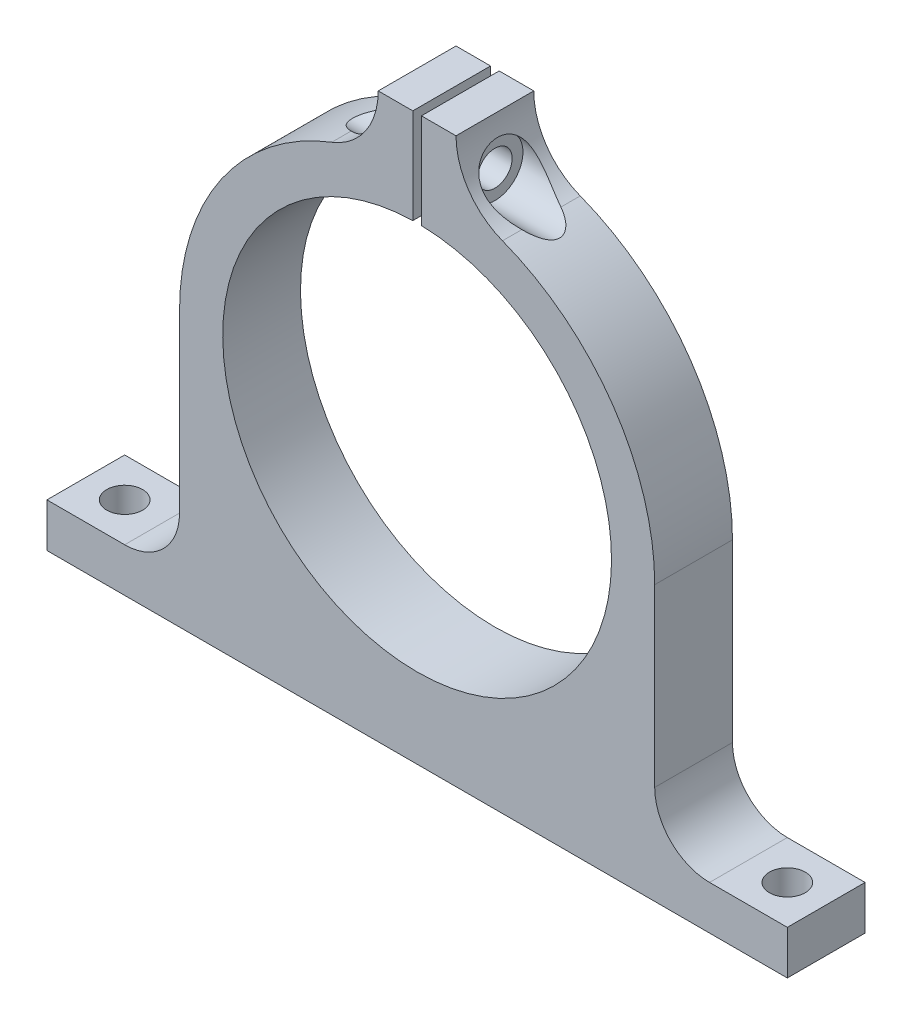
SolidWorks part; units mm, degrees
ref_plane "Front Plane" through (0, 0, 0) normal (0, 0, 1) x (1, 0, 0)
ref_plane "Top Plane" through (0, 0, 0) normal (0, 1, 0) x (1, 0, 0)
ref_plane "Right Plane" through (0, 0, 0) normal (1, 0, 0) x (0, 0, -1)
sketch "Sketch1" plane through (0, 0, 0) normal (0, 0, 1) x (1, 0, 0)
  line L0 (0, 0) -> (0, 55) construction
  line L1 (0, 0) -> (85.7, 0) construction
  line L2 (0, 0) -> (-85.7, 0) construction
  line L3 (85.7, -53.34) -> (85.7, -63.5)
  line L4 (85.7, -63.5) -> (-85.7, -63.5)
  line L5 (-85.7, -63.5) -> (-85.7, -53.34)
  line L6 (0, 55) -> (0, 67) construction
  line L7 (0, 67) -> (1, 67) construction
  line L8 (1, 67) -> (1, 44.9889)
  line L9 (1, 67) -> (9, 67)
  line L10 (-45, 0) -> (-55, 0) construction
  line L11 (0, 67) -> (-1, 67) construction
  line L12 (-1, 67) -> (-1, 44.9889)
  line L13 (-1, 67) -> (-9, 67)
  line L14 (-55, 0) -> (-55, -40.64)
  line L15 (-67.7, -53.34) -> (-85.7, -53.34)
  line L16 (55, 0) -> (55, -40.64)
  line L17 (67.7, -53.34) -> (85.7, -53.34)
  arc A0 (-1, 44.9889) -> (1, 44.9889) centre (0, 0) ccw
  arc A1 (55, 0) -> (19.76, 51.3278) centre (0, 0) ccw
  arc A2 (-19.76, 51.3278) -> (-55, 0) centre (0, 0) ccw
  arc A3 (9, 67) -> (19.76, 51.3278) centre (25.7935, 67) ccw
  arc A4 (55, -40.64) -> (67.7, -53.34) centre (67.7, -40.64) ccw
  arc A5 (-55, -40.64) -> (-67.7, -53.34) centre (-67.7, -40.64) cw
  arc A6 (-19.76, 51.3278) -> (-9, 67) centre (-25.7935, 67) ccw
  dimension "D1" = 90
  dimension "D3" = 12.7
  dimension "D4" = 18
  dimension "D2" = 10
  dimension "D5" = 10.16
  dimension "D6" = 12
  dimension "D7" = 1
  dimension "D8" = 8
  dimension "D9" = 1
  dimension "D10" = 8
  dimension "D11" = 63.5
extrude "Boss-Extrude1" add sketch "Sketch1" along normal blind 18
sketch "Sketch7" plane through (1, 0, 0) normal (-1, 0, 0) x (0, 0, 1)
  line L0 (9, 44.9889) -> (9, 67) construction
  line L1 (18, 44.9889) -> (0, 44.9889) construction
  line L2 (18, 67) -> (0, 67) construction
  circle A0 centre (9, 55.9944) radius 4
  dimension "D1" = 8
extrude "Cut-Extrude4" cut sketch "Sketch7" against normal through all and the other way through all
ref_plane "Plane2" through (-9, 0, 0) normal (1, 0, 0) x (0, 0, -1)
sketch "Sketch8" plane through (-9, 0, 0) normal (1, 0, 0) x (0, 0, -1)
  circle A0 centre (-9, 55.9944) radius 6.5
  dimension "D1" = 13
extrude "Cut-Extrude5" cut sketch "Sketch8" against normal blind 18
ref_plane "Plane3" through (9, 0, 0) normal (-1, 0, 0) x (0, 0, 1)
sketch "Sketch10" plane through (9, 0, 0) normal (-1, 0, 0) x (0, 0, 1)
  circle A0 centre (9, 55.9944) radius 6.5
  dimension "D1" = 13
extrude "Cut-Extrude6" cut sketch "Sketch10" against normal blind 18
sketch "Sketch11" plane through (0, -53.34, 0) normal (0, 1, 0) x (1, 0, 0)
  line L0 (-76.7, 0) -> (-76.7, -18) construction
  line L1 (-67.7, 0) -> (-85.7, 0) construction
  line L2 (-67.7, -18) -> (-85.7, -18) construction
  line L3 (76.7, 0) -> (76.7, -18) construction
  line L4 (85.7, 0) -> (67.7, 0) construction
  line L5 (85.7, -18) -> (67.7, -18) construction
  circle A0 centre (-76.7, -9) radius 4.15
  circle A1 centre (76.7, -9) radius 4.15
  dimension "D1" = 8.3
extrude "Cut-Extrude7" cut sketch "Sketch11" against normal through all
